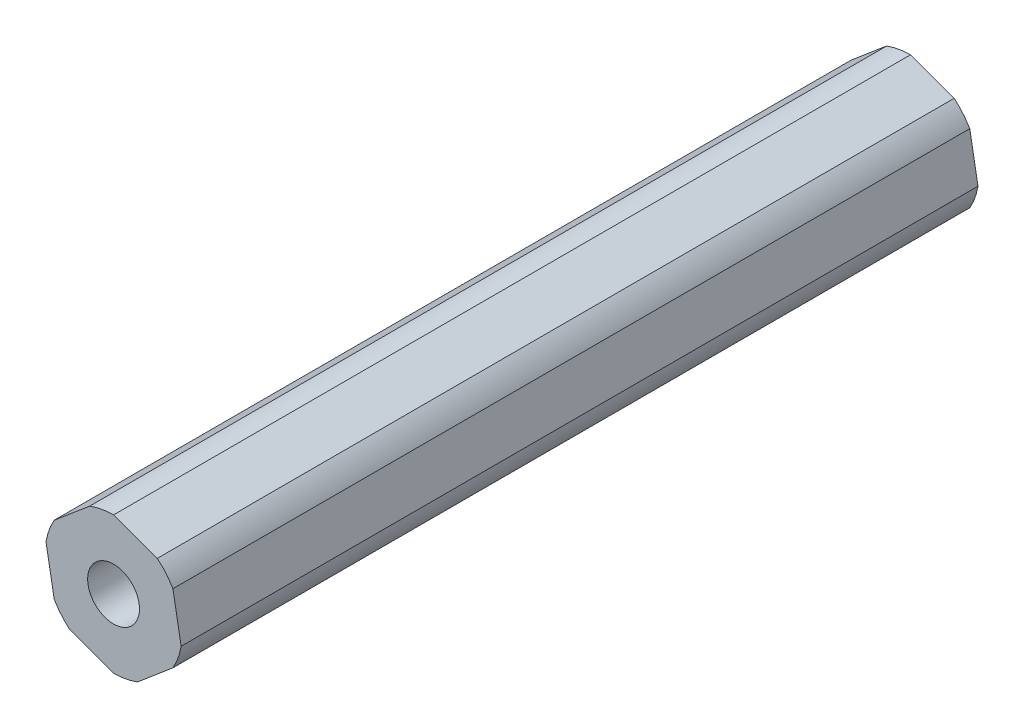
SolidWorks part; units mm, degrees
material "7075-T6 (SN)"
ref_plane "Front Plane" through (0, 0, 0) normal (0, 0, 1) x (1, 0, 0)
ref_plane "Top Plane" through (0, 0, 0) normal (0, 1, 0) x (1, 0, 0)
ref_plane "Right Plane" through (0, 0, 0) normal (1, 0, 0) x (0, 0, -1)
sketch "Sketch1" plane through (0, 0, 0) normal (0, 0, 1) x (1, 0, 0)
  line L1 (-6.6545, 1.1312) -> (-5.8457, -3.375)
  line L2 (-4.3069, -5.1974) -> (0, -6.75)
  line L3 (2.3476, -6.3286) -> (5.8457, -3.375)
  line L4 (6.6545, -1.1312) -> (5.8457, 3.375)
  line L5 (4.3069, 5.1974) -> (0, 6.75)
  line L6 (-2.3476, 6.3286) -> (-5.8457, 3.375)
  circle A0 centre (0, 0) radius 6.35 construction
  arc A1 (-5.8457, 3.375) -> (-6.6545, 1.1312) centre (0, 0) ccw
  arc A2 (-5.8457, -3.375) -> (-4.3069, -5.1974) centre (0, 0) ccw
  arc A3 (0, -6.75) -> (2.3476, -6.3286) centre (0, 0) ccw
  arc A4 (5.8457, -3.375) -> (6.6545, -1.1312) centre (0, 0) ccw
  arc A5 (5.8457, 3.375) -> (4.3069, 5.1974) centre (0, 0) ccw
  arc A6 (0, 6.75) -> (-2.3476, 6.3286) centre (0, 0) ccw
  dimension "D1" = 12.7
  dimension "D2" = 13.5
extrude "Boss-Extrude1" add sketch "Sketch1" along normal blind 78.486
sketch "Sketch2" plane through (0, 0, 78.486) normal (0, 0, 1) x (1, 0, 0)
  circle A0 centre (0, 0) radius 2.0193
  dimension "D1" = 4.0386
extrude "Cut-Extrude1" cut sketch "Sketch2" against normal through all
hole_wizard "1/4-20 Tapped Hole1" positions "Sketch5" profile "Sketch6" tap size "1/4-20" standard "ANSI Inch"
sketch "Sketch5" plane through (0, 0, 78.486) normal (0, 0, 1) x (1, 0, 0)
  point P0 (0, 0)
sketch "Sketch6" plane through (0, 0, 78.486) normal (1, 0, 0) x (0, -1, 0)
  line L0 (0, 0) -> (0, 20.5838)
  line L1 (0, 20.5838) -> (2.5527, 19.05)
  line L2 (2.5527, 19.05) -> (2.5527, 0)
  line L5 (2.5527, 0) -> (0, 0)
  line L10 (0, 20.5838) -> (-2.5527, 19.05) construction
  line L11 (0, -6.35) -> (0, 107.95) construction
  dimension "Tap Drill Dia." = 5.1054
  dimension "Tap Drill Depth" = 19.05
  dimension "Drill Angle" = 118
cosmetic thread "Hole Thread1" parameters "D1"=12.7, "D2"=6.35
hole_wizard "1/4-20 Tapped Hole2" positions "Sketch7" profile "Sketch8" tap size "1/4-20" standard "ANSI Inch"
sketch "Sketch7" plane through (0, 0, 0) normal (0, 0, -1) x (-1, 0, 0)
  point P0 (0, 0)
sketch "Sketch8" plane through (0, 0, 0) normal (1, 0, 0) x (0, 1, 0)
  line L0 (0, 0) -> (0, 20.5838)
  line L1 (0, 20.5838) -> (2.5527, 19.05)
  line L2 (2.5527, 19.05) -> (2.5527, 0)
  line L5 (2.5527, 0) -> (0, 0)
  line L10 (0, 20.5838) -> (-2.5527, 19.05) construction
  line L11 (0, -6.35) -> (0, 107.95) construction
  dimension "Tap Drill Dia." = 5.1054
  dimension "Tap Drill Depth" = 19.05
  dimension "Drill Angle" = 118
cosmetic thread "Hole Thread2" parameters "D1"=12.7, "D2"=6.35
